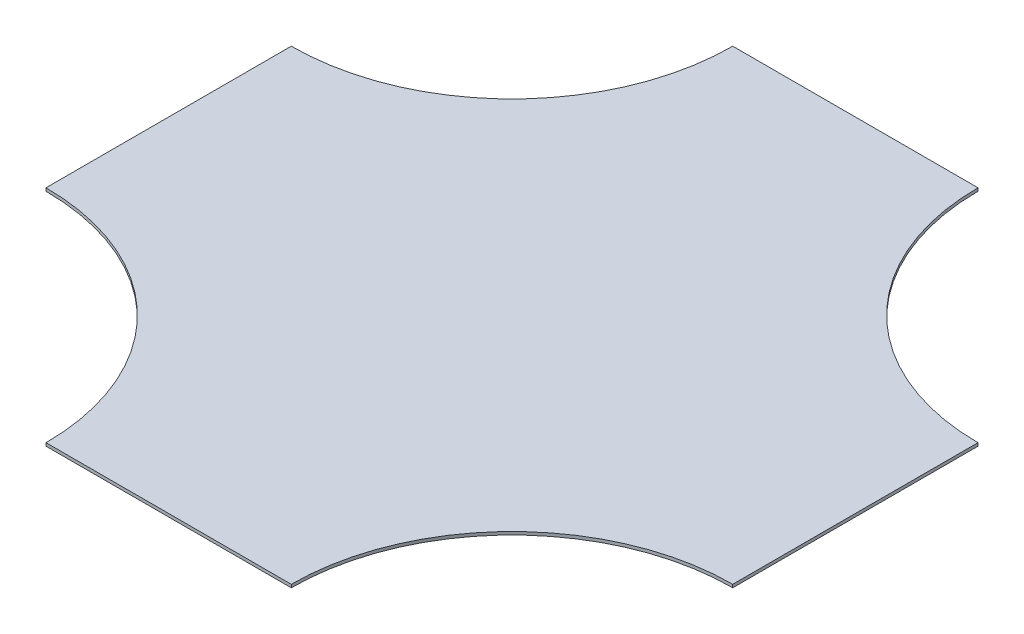
SolidWorks part; units mm, degrees
ref_plane "Front Plane" through (0, 0, 0) normal (0, 0, 1) x (1, 0, 0)
ref_plane "Top Plane" through (0, 0, 0) normal (0, 1, 0) x (1, 0, 0)
ref_plane "Right Plane" through (0, 0, 0) normal (1, 0, 0) x (0, 0, -1)
sketch "Sketch1" plane through (0, 0, 0) normal (0, 1, 0) x (1, 0, 0)
  line L9 (-127, -355.6) -> (127, -355.6)
  line L10 (-355.6, -127) -> (-355.6, 127)
  line L11 (-127, 355.6) -> (127, 355.6)
  line L12 (355.6, -127) -> (355.6, 127)
  line L13 (-193.9554, -193.9554) -> (193.9554, 193.9554) construction
  line L14 (-193.9554, 193.9554) -> (193.9554, -193.9554) construction
  arc A8 (-355.6, 127) -> (-127, 355.6) centre (-355.6, 355.6) ccw
  arc A9 (127, 355.6) -> (355.6, 127) centre (355.6, 355.6) ccw
  arc A10 (355.6, -127) -> (127, -355.6) centre (355.6, -355.6) ccw
  arc A11 (-127, -355.6) -> (-355.6, -127) centre (-355.6, -355.6) ccw
  point P0 (0, 0)
  dimension "D3" = 457.2
  dimension "D4" = 457.2
  dimension "D5" = 457.2
  dimension "D6" = 457.2
  dimension "D1" = 711.2
  dimension "D2" = 711.2
extrude "Boss-Extrude1" add sketch "Sketch1" along normal blind 3.175
